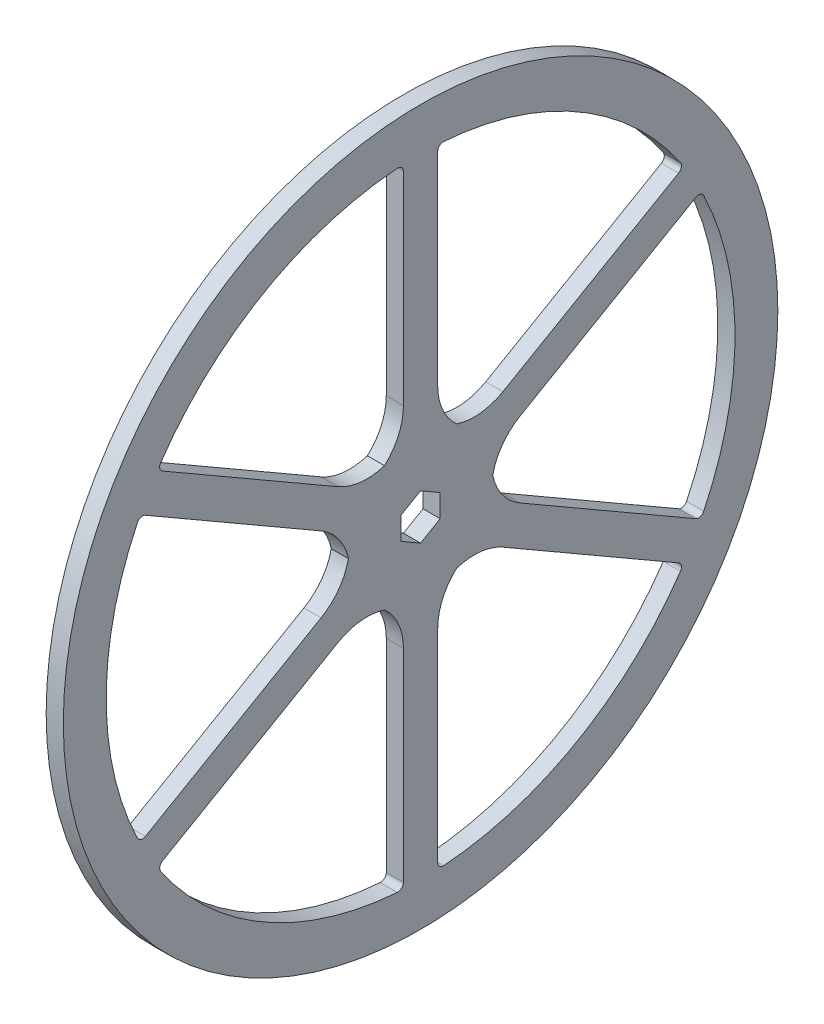
SolidWorks part; units mm, degrees
material "1023 Carbon Steel Sheet (SS)"
ref_plane "Front Plane" through (0, 0, 0) normal (0, 0, 1) x (1, 0, 0)
ref_plane "Top Plane" through (0, 0, 0) normal (0, 1, 0) x (1, 0, 0)
ref_plane "Right Plane" through (0, 0, 0) normal (1, 0, 0) x (0, 0, -1)
sketch "Sketch1" plane through (0, 0, 0) normal (1, 0, 0) x (0, 0, -1)
  circle A0 centre (0, 0) radius 62.5
  dimension "D1" = 125
extrude "Boss-Extrude1" add sketch "Sketch1" along normal blind 3
sketch "Sketch6" plane through (0, 0, 0) normal (-1, 0, 0) x (0, 0, 1)
  line L0 (-3, 54.9181) -> (-3, 12.1347)
  line L1 (-46.0605, 30.0571) -> (-9.0089, 8.6654)
  line L2 (0, -1.65) -> (0, 1.65) construction
  arc A0 (-3, 54.9181) -> (-46.0605, 30.0571) centre (0, 0) ccw
  arc A2 (-3, 12.1347) -> (-9.0089, 8.6654) centre (0, 0) ccw
  dimension "D1" = 110
  dimension "D6" = 25
  dimension "D3" = 3
  dimension "D4" = 3
  dimension "D5" = 60
extrude "Cut-Extrude5" cut sketch "Sketch6" against normal through all
pattern_circular "CirPattern4" count 6 every 60 about axis through (3, 0, 0) along (-1, 0, 0) of "Cut-Extrude5"
sketch "Sketch7" plane through (0, 0, 0) normal (-1, 0, 0) x (0, 0, 1)
  line L1 (0, 3.9606) -> (-3.43, 1.9803)
  line L2 (-3.43, 1.9803) -> (-3.43, -1.9803)
  line L3 (-3.43, -1.9803) -> (0, -3.9606)
  line L4 (0, -3.9606) -> (3.43, -1.9803)
  line L5 (3.43, -1.9803) -> (3.43, 1.9803)
  line L6 (3.43, 1.9803) -> (0, 3.9606)
  circle A0 centre (0, 0) radius 3.43 construction
  dimension "D1" = 6.86
extrude "Cut-Extrude6" cut sketch "Sketch7" against normal through all
fillet "Fillet1" radius 10 12 edges at (1.5, 12.1347, 3) (1.5, 8.6654, 9.0089) (1.5, 3.4693, 12.0089) (1.5, -3.4693, 12.0089) (1.5, -8.6654, 9.0089) (1.5, -12.1347, 3) (1.5, -12.1347, -3) (1.5, -8.6654, -9.0089) (1.5, -3.4693, -12.0089) (1.5, 3.4693, -12.0089) (1.5, 8.6654, -9.0089) (1.5, 12.1347, -3)
fillet "Fillet2" radius 1 12 edges at (1.5, -24.861, -49.0605) (1.5, -30.0571, -46.0605) (1.5, -54.9181, -3) (1.5, -54.9181, 3) (1.5, -30.0571, 46.0605) (1.5, -24.861, 49.0605) (1.5, 24.861, 49.0605) (1.5, 30.0571, 46.0605) (1.5, 54.9181, 3) (1.5, 24.861, -49.0605) (1.5, 30.0571, -46.0605) (1.5, 54.9181, -3)
